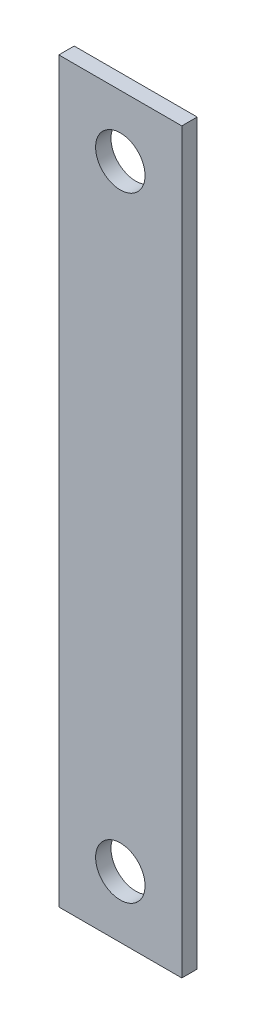
SolidWorks part; units mm, degrees
ref_plane "Front Plane" through (0, 0, 0) normal (0, 0, 1) x (1, 0, 0)
ref_plane "Top Plane" through (0, 0, 0) normal (0, 1, 0) x (1, 0, 0)
ref_plane "Right Plane" through (0, 0, 0) normal (1, 0, 0) x (0, 0, -1)
sketch "Sketch1" plane through (0, 0, 0) normal (0, 0, 1) x (1, 0, 0)
  line L1 (0, 0) -> (12.7, 0)
  line L2 (0, 0) -> (0, 76.2)
  line L3 (0, 76.2) -> (12.7, 76.2)
  line L4 (12.7, 0) -> (12.7, 76.2)
  dimension "D1" = 76.2
  dimension "D2" = 12.7
base flange "Base-Flange1" sketch "Sketch1" thickness 1.5875 reverse thickness direction no parameters "D1"=254
sketch "Sketch8" plane through (0, 0, 0) normal (0, 0, 1) x (1, 0, 0)
  line L0 (6.35, 76.2) -> (6.35, 0) construction
  line L1 (12.7, 76.2) -> (0, 76.2) construction
  line L2 (0, 0) -> (12.7, 0) construction
hole_wizard "#10 Clearance Hole1" positions "Sketch10" profile "Sketch11" hole size "#10" standard "ANSI Inch" end condition through all
sketch "Sketch10" plane through (0, 0, 0) normal (0, 0, 1) x (1, 0, 0)
  line L0 (6.35, 76.2) -> (6.35, 0) construction
  point P0 (6.35, 69.85)
  point P6 (6.35, 6.35)
  dimension "D1" = 6.35
  dimension "D2" = 6.35
sketch "Sketch11" plane through (6.35, 69.85, 0) normal (1, 0, 0) x (0, -1, 0)
  line L0 (0, 0) -> (0, 1.5875)
  line L1 (0, 1.5875) -> (2.5527, 1.5875)
  line L2 (2.5527, 1.5875) -> (2.5527, 0)
  line L5 (2.5527, 0) -> (0, 0)
  line L11 (0, -6.35) -> (0, 107.95) construction
  dimension "Thru Hole Dia." = 5.1054
  dimension "Thru Hole Depth" = 1.5875
sketch "Bend-Lines1" [suppressed] plane through (0, 0, 0) normal (0, 1, 0) x (1, 0, 0)
sketch "Bounding-Box1" [suppressed] plane through (0, 0, 0) normal (0, 1, 0) x (1, 0, 0)
sheet metal parameters "Sheet-Metal1" thickness 1.5875 parameters "D1"=254
flat pattern "Flat-Pattern1" [suppressed]
sketch "Bend-Lines2" plane through (0, 0, 0) normal (0, 1, 0) x (1, 0, 0)
sketch3d "Bounding-Box2" [suppressed]
  line L0 (-12.7, 76.2, 0) -> (-12.7, 0, 0) construction
  line L1 (0, 76.2, 0) -> (0, 0, 0) construction
  line L2 (-12.7, 76.2, 0) -> (0, 76.2, 0) construction
  line L3 (-12.7, 0, 0) -> (0, 0, 0) construction
sheet metal parameters "Sheet-Metal2" thickness 1.5875 parameters "D1"=254
flat pattern "Flat-Pattern1"
sketch "Bend-Lines2" plane through (0, 0, 0) normal (0, 1, 0) x (1, 0, 0)
sketch3d "Bounding-Box2" [suppressed]
  line L0 (12.7, 76.2, 0) -> (12.7, 0, 0) construction
  line L1 (0, 76.2, 0) -> (0, 0, 0) construction
  line L2 (12.7, 76.2, 0) -> (0, 76.2, 0) construction
  line L3 (12.7, 0, 0) -> (0, 0, 0) construction
